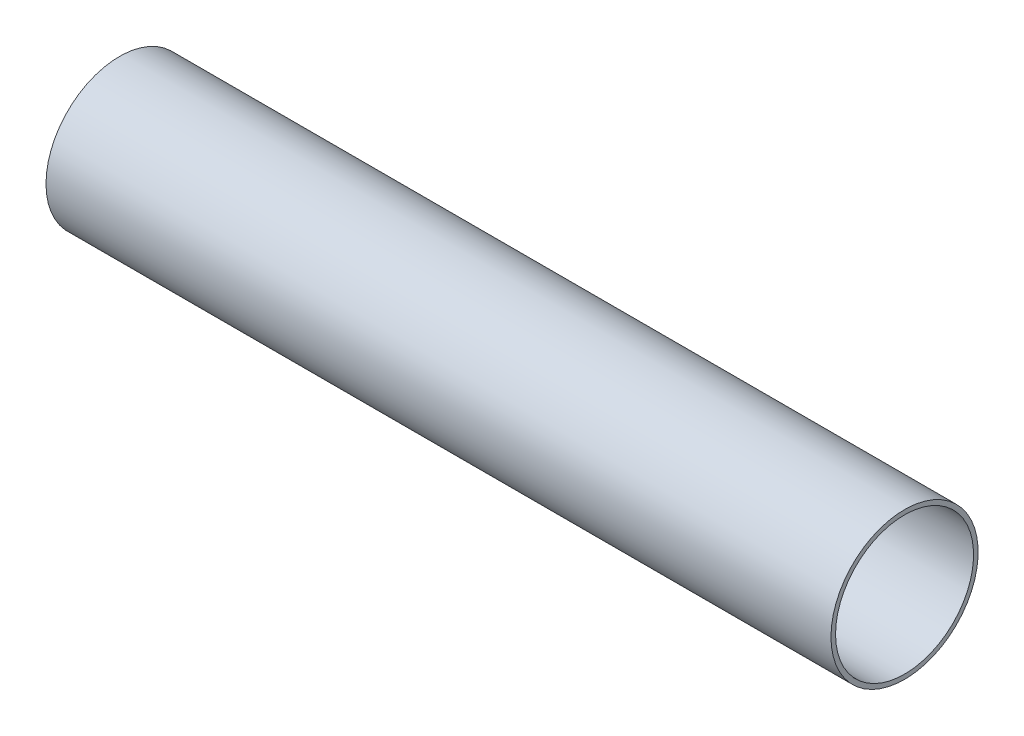
SolidWorks part; units mm, degrees
ref_plane "Front Plane" through (0, 0, 0) normal (0, 0, 1) x (1, 0, 0)
ref_plane "Top Plane" through (0, 0, 0) normal (0, 1, 0) x (1, 0, 0)
ref_plane "Right Plane" through (0, 0, 0) normal (1, 0, 0) x (0, 0, -1)
sketch "Sketch1" plane through (0, 0, 0) normal (1, 0, 0) x (0, 0, -1)
  circle A0 centre (0, 0) radius 14.2875
  circle A1 centre (0, 0) radius 13.3985
extrude "Boss-Extrude1" add sketch "Sketch1" along normal mid plane 152.4
